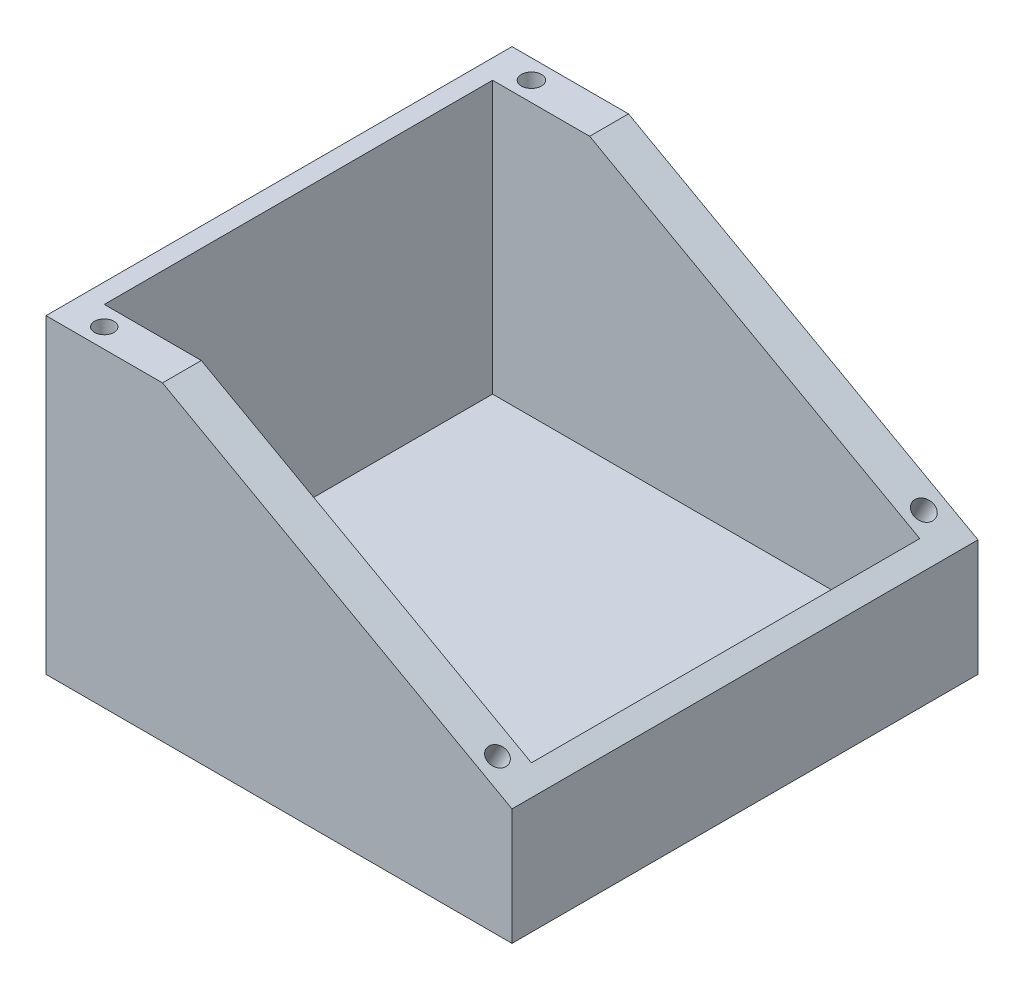
SolidWorks part; units mm, degrees
ref_plane "Front Plane" through (0, 0, 0) normal (0, 0, 1) x (1, 0, 0)
ref_plane "Top Plane" through (0, 0, 0) normal (0, 1, 0) x (1, 0, 0)
ref_plane "Right Plane" through (0, 0, 0) normal (1, 0, 0) x (0, 0, -1)
sketch "Sketch1" plane through (0, 0, 0) normal (0, 0, 1) x (1, 0, 0)
  line L0 (0, 0) -> (0, 101.6)
  line L1 (0, 101.6) -> (152.4, 101.6)
  line L2 (152.4, 101.6) -> (152.4, 0)
  line L3 (152.4, 0) -> (0, 0)
  dimension "D1" = 101.6
  dimension "D2" = 152.4
extrude "Boss-Extrude1" add sketch "Sketch1" along normal blind 152.4
sketch "Sketch6" plane through (0, 0, 152.4) normal (0, 0, 1) x (1, 0, 0)
  line L0 (38.1, 101.6) -> (152.4, 101.6)
  line L1 (152.4, 101.6) -> (0, 101.6) construction
  line L2 (152.4, 101.6) -> (152.4, 38.1)
  line L3 (152.4, 0) -> (152.4, 101.6) construction
  line L4 (152.4, 38.1) -> (38.1, 101.6)
  line L5 (104.4367, 101.6) -> (104.5902, 101.6)
  line M5 (152.4, 0) -> (152.4, 101.6)
  line M6 (152.4, 101.6) -> (0, 101.6)
  dimension "D1" = 63.5
  dimension "D2" = 114.3
extrude "Cut-Extrude2" cut sketch "Sketch6" against normal blind 152.4 contours L4 L0 M5 M6 region at (114.3, 80.4333, 152.4)
sketch "Sketch7" plane through (0, 101.6, 0) normal (0, 1, 0) x (1, 0, 0)
  line L0 (6.35, -12.7) -> (6.35, -139.7)
  line L1 (6.35, -139.7) -> (146.05, -139.7)
  line L2 (146.05, -139.7) -> (146.05, -12.7)
  line L3 (146.05, -12.7) -> (6.35, -12.7)
  line L4 (38.1, 0) -> (0, 0) construction
  line L5 (0, -152.4) -> (0, 0) construction
  line L6 (152.4, -152.4) -> (38.1, -152.4) construction
  line L7 (152.4, 0) -> (152.4, -152.4) construction
  dimension "D1" = 12.7
  dimension "D2" = 6.35
  dimension "D3" = 12.7
  dimension "D4" = 6.35
extrude "Cut-Extrude3" cut sketch "Sketch7" against normal blind 88.9
sketch "Sketch8" plane through (0, 101.6, 0) normal (0, 1, 0) x (1, 0, 0)
  line L0 (38.1, -152.4) -> (0, -152.4) construction
  line L1 (0, -152.4) -> (0, 0) construction
  line L2 (38.1, 0) -> (0, 0) construction
  circle A0 centre (12.7, -146.05) radius 3.175
  circle A1 centre (12.7, -6.35) radius 3.302
  dimension "D1" = 6.35
  dimension "D2" = 6.604
  dimension "D4" = 12.7
  dimension "D3" = 6.35
  dimension "D5" = 6.35
  dimension "D6" = 12.7
extrude "Cut-Extrude4" cut sketch "Sketch8" against normal blind 12.7
sketch "Sketch9" plane through (52.1179, 93.8123, 0) normal (0.4856, 0.8742, 0) x (0.8742, -0.4856, 0)
  line L0 (114.7186, -152.4) -> (-16.0359, -152.4) construction
  line L1 (114.7186, 0) -> (-16.0359, 0) construction
  line L2 (114.7186, 0) -> (114.7186, -152.4) construction
  circle A0 centre (102.0186, -146.05) radius 3.175
  circle A1 centre (102.0186, -6.604) radius 3.302
  dimension "D1" = 6.604
  dimension "D2" = 6.35
  dimension "D3" = 6.35
  dimension "D4" = 6.604
  dimension "D5" = 12.7
  dimension "D6" = 12.7
extrude "Cut-Extrude5" cut sketch "Sketch9" against normal blind 12.7
